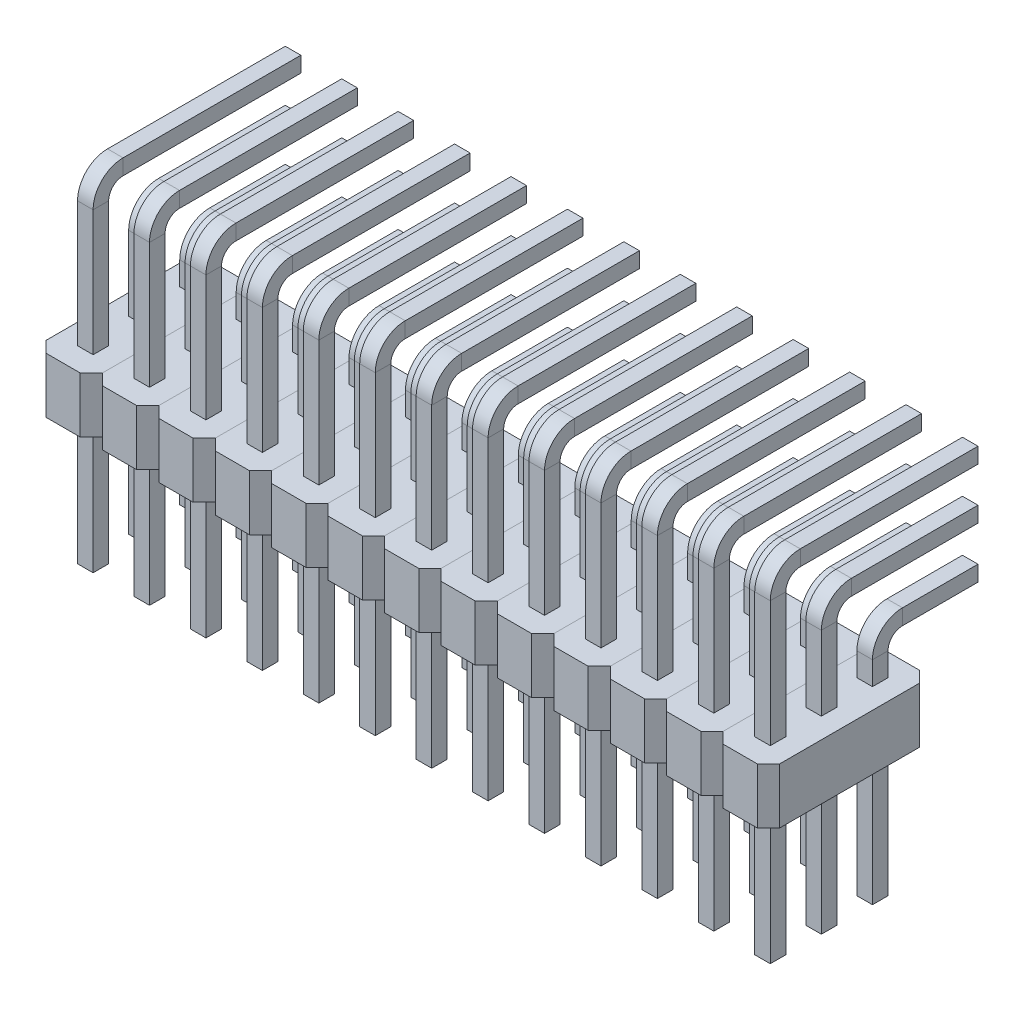
SolidWorks part; units mm, degrees
note: The reader was unsure of these and kept them because the rebuilt part matched: shared geometry of "Sketch1<5>", "Sketch2<6>", "Sketch1<6>", "Sketch2<7>", "Sketch1<7>".
material "201 Annealed Stainless Steel (SS)"
ref_plane "Front Plane" through (0, 0, 0) normal (0, 0, 1) x (1, 0, 0)
ref_plane "Top Plane" through (0, 0, 0) normal (0, 1, 0) x (1, 0, 0)
ref_plane "Right Plane" through (0, 0, 0) normal (1, 0, 0) x (0, 0, -1)
sketch "Sketch1" plane through (0, 0, 0) normal (0, 1, 0) x (1, 0, 0)
  line L0 (0, 0) -> (2.54, 0)
  line L1 (0, 0) -> (0, -7.3)
  line L2 (0, -7.3) -> (2.54, -7.3)
  line L3 (2.54, 0) -> (2.54, -7.3)
  line L4 (0.92, -1) -> (1.62, -1)
  line L5 (0.92, -1) -> (0.92, -1.7)
  line L6 (0.92, -1.7) -> (1.62, -1.7)
  line L7 (1.62, -1) -> (1.62, -1.7)
  line L8 (0.92, -5.6) -> (1.62, -5.6)
  line L9 (0.92, -5.6) -> (0.92, -6.3)
  line L10 (0.92, -6.3) -> (1.62, -6.3)
  line L11 (1.62, -5.6) -> (1.62, -6.3)
  line L12 (0.92, -3.3) -> (1.62, -3.3)
  line L13 (0.92, -3.3) -> (0.92, -4)
  line L14 (0.92, -4) -> (1.62, -4)
  line L15 (1.62, -3.3) -> (1.62, -4)
  dimension "D1" = 7.3
  dimension "D2" = 2.54
  dimension "D3" = 0.92
  dimension "D4" = 1
  dimension "D5" = 0.7
  dimension "D6" = 1.6
  dimension "D7" = 1.6
ref_plane "Plane1" through (1.25, 0, 0) normal (1, 0, 0) x (0, 0, -1)
sketch "Sketch2" plane through (1.25, 0, 0) normal (1, 0, 0) x (0, 0, -1)
  line L0 (-5.95, 8.15) -> (-5.95, -6)
  line L1 (-3.65, 5.85) -> (-3.65, -6)
  line L2 (-1.35, 3.55) -> (-1.35, -6)
  line L3 (-4.95, 9.15) -> (3.05, 9.15)
  line L4 (0, 0) -> (-7.3, 0) construction
  line L5 (-2.65, 6.85) -> (3.05, 6.85)
  line L6 (-0.35, 4.55) -> (3.05, 4.55)
  arc A0 (-1.35, 3.55) -> (-0.35, 4.55) centre (-0.35, 3.55) cw
  arc A1 (-3.65, 5.85) -> (-2.65, 6.85) centre (-2.65, 5.85) cw
  arc A2 (-5.95, 8.15) -> (-4.95, 9.15) centre (-4.95, 8.15) cw
  point P19 (-5.95, 9.15)
  dimension "D9" = 1
  dimension "D1" = 15.15
  dimension "D2" = 2.3
  dimension "D3" = 2.3
  dimension "D4" = 1.35
  dimension "D5" = 6
  dimension "D6" = 9
  dimension "D7" = 2.3
  dimension "D8" = 2.3
sweep "Sweep3" add profiles "Sketch1" path "Sketch2"
sweep "Sweep4" add profiles "Sketch1<5>" path "Sketch2<6>"
sketch "Sketch1<5>" plane through (0, 0, 0) normal (0, 1, 0) x (1, 0, 0) same geometry as "Sketch1"
sketch "Sketch2<6>" plane through (1.25, 0, 0) normal (1, 0, 0) x (0, 0, -1) same geometry as "Sketch2"
sweep "Sweep5" add profiles "Sketch1<6>" path "Sketch2<7>"
sketch "Sketch1<6>" plane through (0, 0, 0) normal (0, 1, 0) x (1, 0, 0) same geometry as "Sketch1"
sketch "Sketch2<7>" plane through (1.25, 0, 0) normal (1, 0, 0) x (0, 0, -1) same geometry as "Sketch2"
extrude "Boss-Extrude1" add sketch "Sketch1<7>" along normal blind 2.5 separate body contours L3 L0 L1 L2 L4 L7 L6 L5 L8 L11 L10 L9 L12 L15 L14 L13
sketch "Sketch1<7>" plane through (0, 0, 0) normal (0, 1, 0) x (1, 0, 0) same geometry as "Sketch1"
chamfer "Chamfer1" distance 0.5 angle 45 4 edges at (0, 1.25, 0) (2.54, 1.25, 0) (0, 1.25, 7.3) (2.54, 1.25, 7.3)
pattern_linear "LPattern1" count 13 spacing 2.54 along (1, 0, 0) of bodies 104 103 102 101
